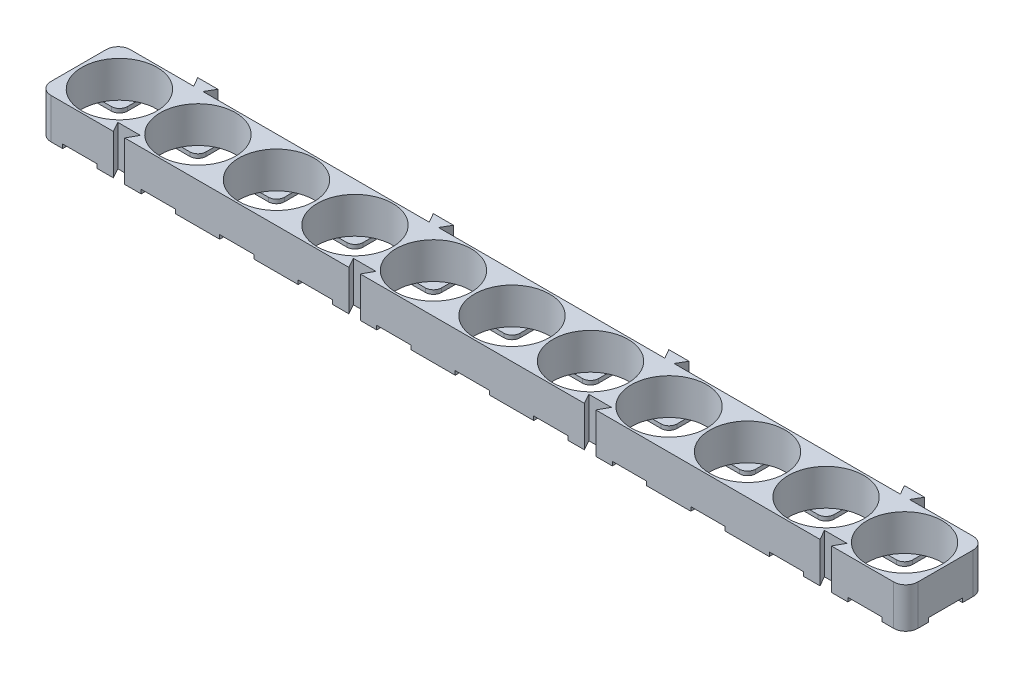
SolidWorks part; units mm, degrees
ref_plane "Front Plane" through (0, 0, 0) normal (0, 0, 1) x (1, 0, 0)
ref_plane "Top Plane" through (0, 0, 0) normal (0, 1, 0) x (1, 0, 0)
ref_plane "Right Plane" through (0, 0, 0) normal (1, 0, 0) x (0, 0, -1)
sketch "Sketch3" plane through (0, 0, 0) normal (0, 1, 0) x (1, 0, 0)
  line L0 (-10.15, 0) -> (9.35, 0) construction
  line L5 (9.35, 9.35) -> (9.35, -9.35) construction
  line L6 (9.35, -9.35) -> (-9.35, -9.35) construction
  line L7 (-9.35, -9.35) -> (-9.35, 9.35) construction
  line L8 (-9.35, 9.35) -> (9.35, 9.35) construction
  line L9 (10.15, -9.35) -> (10.15, 9.35) construction
  line L10 (10.15, 9.35) -> (28.85, 9.35) construction
  line L11 (28.85, 9.35) -> (28.85, -9.35) construction
  line L12 (28.85, -9.35) -> (10.15, -9.35) construction
  line L13 (29.65, -9.35) -> (29.65, 9.35) construction
  line L14 (29.65, 9.35) -> (48.35, 9.35) construction
  line L15 (48.35, 9.35) -> (48.35, -9.35) construction
  line L16 (48.35, -9.35) -> (29.65, -9.35) construction
  line L17 (49.15, -9.35) -> (49.15, 9.35) construction
  line L18 (49.15, 9.35) -> (67.85, 9.35) construction
  line L19 (67.85, 9.35) -> (67.85, -9.35) construction
  line L20 (67.85, -9.35) -> (49.15, -9.35) construction
  line L21 (68.65, -9.35) -> (68.65, 9.35) construction
  line L22 (68.65, 9.35) -> (87.35, 9.35) construction
  line L23 (87.35, 9.35) -> (87.35, -9.35) construction
  line L24 (87.35, -9.35) -> (68.65, -9.35) construction
  line L25 (88.15, -9.35) -> (88.15, 9.35) construction
  line L26 (88.15, 9.35) -> (106.85, 9.35) construction
  line L27 (106.85, 9.35) -> (106.85, -9.35) construction
  line L28 (106.85, -9.35) -> (88.15, -9.35) construction
  line L29 (107.65, -9.35) -> (107.65, 9.35) construction
  line L30 (107.65, 9.35) -> (126.35, 9.35) construction
  line L31 (126.35, 9.35) -> (126.35, -9.35) construction
  line L32 (126.35, -9.35) -> (107.65, -9.35) construction
  line L33 (127.15, -9.35) -> (127.15, 9.35) construction
  line L34 (127.15, 9.35) -> (145.85, 9.35) construction
  line L35 (145.85, 9.35) -> (145.85, -9.35) construction
  line L36 (145.85, -9.35) -> (127.15, -9.35) construction
  line L37 (146.65, -9.35) -> (146.65, 9.35) construction
  line L38 (146.65, 9.35) -> (165.35, 9.35) construction
  line L39 (165.35, 9.35) -> (165.35, -9.35) construction
  line L40 (165.35, -9.35) -> (146.65, -9.35) construction
  line L41 (166.15, -9.35) -> (166.15, 9.35) construction
  line L42 (166.15, 9.35) -> (184.85, 9.35) construction
  line L43 (184.85, 9.35) -> (184.85, -9.35) construction
  line L44 (184.85, -9.35) -> (166.15, -9.35) construction
  line L45 (185.65, -9.35) -> (185.65, 9.35) construction
  line L46 (185.65, 9.35) -> (204.35, 9.35) construction
  line L47 (204.35, 9.35) -> (204.35, -9.35) construction
  line L48 (204.35, -9.35) -> (185.65, -9.35) construction
  line L49 (-10.15, 0) -> (205.15, 0) construction
  line L50 (-10.15, 9.85) -> (205.15, 9.85)
  line L51 (-10.15, 9.85) -> (-10.15, -9.85)
  line L52 (-10.15, -9.85) -> (205.15, -9.85)
  line L53 (205.15, 9.85) -> (205.15, -9.85)
  line L54 (9.35, 9.35) -> (10.15, 9.35) construction
  line L55 (9.75, 28.55) -> (9.75, -9.85) construction
  line L56 (67.85, 9.35) -> (68.65, 9.35) construction
  line L57 (68.25, 9.35) -> (68.25, 13.7208) construction
  line L58 (12.25, 12.2) -> (7.25, 12.2)
  line L59 (7.25, 12.2) -> (8.6068, 9.85)
  line L60 (8.6068, 9.85) -> (10.8932, 9.85)
  line L61 (12.25, 12.2) -> (10.8932, 9.85)
  line L62 (12.55, -7.35) -> (6.95, -7.35)
  line L63 (6.95, -7.35) -> (8.3358, -9.85)
  line L64 (8.3358, -9.85) -> (11.1642, -9.85)
  line L65 (12.55, -7.35) -> (11.1642, -9.85)
  line L66 (67.1068, 9.85) -> (69.3932, 9.85)
  line L67 (70.75, 12.2) -> (69.3932, 9.85)
  line L68 (70.75, 12.2) -> (65.75, 12.2)
  line L69 (65.75, 12.2) -> (67.1068, 9.85)
  line L70 (66.8358, -9.85) -> (69.6642, -9.85)
  line L71 (71.05, -7.35) -> (69.6642, -9.85)
  line L72 (71.05, -7.35) -> (65.45, -7.35)
  line L73 (65.45, -7.35) -> (66.8358, -9.85)
  line L74 (125.6068, 9.85) -> (127.8932, 9.85)
  line L75 (129.25, 12.2) -> (127.8932, 9.85)
  line L76 (129.25, 12.2) -> (124.25, 12.2)
  line L77 (124.25, 12.2) -> (125.6068, 9.85)
  line L78 (125.3358, -9.85) -> (128.1642, -9.85)
  line L79 (129.55, -7.35) -> (128.1642, -9.85)
  line L80 (129.55, -7.35) -> (123.95, -7.35)
  line L81 (123.95, -7.35) -> (125.3358, -9.85)
  line L82 (184.1068, 9.85) -> (186.3932, 9.85)
  line L83 (187.75, 12.2) -> (186.3932, 9.85)
  line L84 (187.75, 12.2) -> (182.75, 12.2)
  line L85 (182.75, 12.2) -> (184.1068, 9.85)
  line L86 (183.8358, -9.85) -> (186.6642, -9.85)
  line L87 (188.05, -7.35) -> (186.6642, -9.85)
  line L88 (188.05, -7.35) -> (182.45, -7.35)
  line L89 (182.45, -7.35) -> (183.8358, -9.85)
  line L90 (68.25, 12.2) -> (68.25, 9.85) construction
  circle A0 centre (0, 0) radius 9.35
  circle A1 centre (19.5, 0) radius 9.35
  circle A2 centre (39, 0) radius 9.35
  circle A3 centre (58.5, 0) radius 9.35
  circle A4 centre (78, 0) radius 9.35
  circle A5 centre (97.5, 0) radius 9.35
  circle A6 centre (117, 0) radius 9.35
  circle A7 centre (136.5, 0) radius 9.35
  circle A8 centre (156, 0) radius 9.35
  circle A9 centre (175.5, 0) radius 9.35
  circle A10 centre (195, 0) radius 9.35
  point P10 (-0.4, 0)
  point P13 (-9.35, 0)
  point P16 (0, 9.35)
  point P84 (9.75, 9.35)
  point P88 (9.75, 9.85)
  point P89 (9.75, 12.2)
  point P94 (9.75, -7.35)
  dimension "D1" = 18.7
  dimension "D2" = 11
  dimension "D3" = 0.8
  dimension "D4" = 0.5
  dimension "D5" = 0.8
  dimension "D6" = 0.8
  dimension "D7" = 215.3
  dimension "D8" = 19.7
  dimension "D9" = 5
  dimension "D10" = 60
  dimension "D11" = 2.35
  dimension "D12" = 5.6
  dimension "D13" = 61
  dimension "D14" = 2.5
  dimension "D16" = 19.7
  dimension "D15" = 4
extrude "Boss-Extrude3" add sketch "Sketch3" along normal blind 10 contours L89 L88 L87 L52 L53 L50 L51 L63 L62 L65 L73 L72 L71 L81 L80 L79 A10 A9 A8 A7 A6 A5 A4 A3 A2 A1 A0 | L61 L58 L59 L50 | L68 L69 L50 L67 | L76 L77 L50 L75 | L84 L85 L50 L83 region at (-0.7716, 0, -9.6338) region at (9.75, 0, -11.1709) region at (68.25, 0, -11.1709) region at (126.75, 0, -11.1709) region at (185.25, 0, -11.1709)
extrude "Boss-Extrude6" add sketch "Sketch3<4>" along normal blind 1 contours A0 | A1 | A2 | A3 | A4 | A5 | A6 | A7 | A8 | A9 | A10 region at (0, 0, 0) region at (19.5, 0, 0) region at (39, 0, 0) region at (58.5, 0, 0) region at (78, 0, 0) region at (97.5, 0, 0) region at (117, 0, 0) region at (136.5, 0, 0) region at (156, 0, 0) region at (175.5, 0, 0) region at (195, 0, 0)
sketch "Sketch3<4>" plane through (0, 0, 0) normal (0, 1, 0) x (1, 0, 0) same geometry as "Sketch3"
sketch "Sketch8" plane through (0, 1, 0) normal (0, 1, 0) x (1, 0, 0)
  line L0 (-9.35, 0) -> (9.35, 0) construction
  line L1 (0, -9.35) -> (0, 9.35) construction
  line L2 (19.5, -9.35) -> (19.5, 9.35) construction
  line L3 (205.15, 9.85) -> (205.15, -9.85) construction
  line L4 (-10.15, -4.25) -> (205.15, -4.25)
  line L5 (-10.15, -4.25) -> (-10.15, 4.25)
  line L6 (-10.15, 4.25) -> (205.15, 4.25)
  line L7 (205.15, -4.25) -> (205.15, 4.25)
  line L8 (-10.15, -4.25) -> (205.15, 4.25) construction
  line L9 (-10.15, 4.25) -> (205.15, -4.25) construction
  line L10 (-10.15, 9.85) -> (8.6068, 9.85) construction
  line L11 (-4.25, -9.85) -> (4.25, -9.85)
  line L12 (-4.25, -9.85) -> (-4.25, 9.85)
  line L13 (-4.25, 9.85) -> (4.25, 9.85)
  line L14 (4.25, -9.85) -> (4.25, 9.85)
  line L15 (-4.25, -9.85) -> (4.25, 9.85) construction
  line L16 (-4.25, 9.85) -> (4.25, -9.85) construction
  line L17 (15.25, -9.85) -> (15.25, 9.85)
  line L18 (15.25, -9.85) -> (23.75, -9.85)
  line L19 (23.75, -9.85) -> (23.75, 9.85)
  line L20 (15.25, 9.85) -> (23.75, 9.85)
  line L21 (34.75, -9.85) -> (34.75, 9.85)
  line L22 (34.75, -9.85) -> (43.25, -9.85)
  line L23 (43.25, -9.85) -> (43.25, 9.85)
  line L24 (34.75, 9.85) -> (43.25, 9.85)
  line L25 (54.25, -9.85) -> (54.25, 9.85)
  line L26 (54.25, -9.85) -> (62.75, -9.85)
  line L27 (62.75, -9.85) -> (62.75, 9.85)
  line L28 (54.25, 9.85) -> (62.75, 9.85)
  line L29 (73.75, -9.85) -> (73.75, 9.85)
  line L30 (73.75, -9.85) -> (82.25, -9.85)
  line L31 (82.25, -9.85) -> (82.25, 9.85)
  line L32 (73.75, 9.85) -> (82.25, 9.85)
  line L33 (93.25, -9.85) -> (93.25, 9.85)
  line L34 (93.25, -9.85) -> (101.75, -9.85)
  line L35 (101.75, -9.85) -> (101.75, 9.85)
  line L36 (93.25, 9.85) -> (101.75, 9.85)
  line L37 (112.75, -9.85) -> (112.75, 9.85)
  line L38 (112.75, -9.85) -> (121.25, -9.85)
  line L39 (121.25, -9.85) -> (121.25, 9.85)
  line L40 (112.75, 9.85) -> (121.25, 9.85)
  line L41 (132.25, -9.85) -> (132.25, 9.85)
  line L42 (132.25, -9.85) -> (140.75, -9.85)
  line L43 (140.75, -9.85) -> (140.75, 9.85)
  line L44 (132.25, 9.85) -> (140.75, 9.85)
  line L45 (151.75, -9.85) -> (151.75, 9.85)
  line L46 (151.75, -9.85) -> (160.25, -9.85)
  line L47 (160.25, -9.85) -> (160.25, 9.85)
  line L48 (151.75, 9.85) -> (160.25, 9.85)
  line L49 (171.25, -9.85) -> (171.25, 9.85)
  line L50 (171.25, -9.85) -> (179.75, -9.85)
  line L51 (179.75, -9.85) -> (179.75, 9.85)
  line L52 (171.25, 9.85) -> (179.75, 9.85)
  line L53 (190.75, -9.85) -> (190.75, 9.85)
  line L54 (190.75, -9.85) -> (199.25, -9.85)
  line L55 (199.25, -9.85) -> (199.25, 9.85)
  line L56 (190.75, 9.85) -> (199.25, 9.85)
  line L57 (15.25, 9.85) -> (23.75, -9.85) construction
  circle A2 centre (0, 0) radius 9.35
  circle A3 centre (0, 0) radius 9.35 construction
  circle A5 centre (19.5, 0) radius 9.35
  circle A6 centre (19.5, 0) radius 9.35 construction
  point P3 (0, 0)
  point P12 (0, 0)
  point P14 (19.5, 0)
  point P15 (97.5, 0)
  dimension "D3" = 19.5
  dimension "D4" = 8.5
  dimension "D5" = 11
  dimension "D1" = 0
  dimension "D2" = 0
extrude "Cut-Extrude4" cut sketch "Sketch8" against normal through all contours L6 L7 L4 L5 | L12 L13 L14 L11 | L17 L20 L19 L18 | L21 L24 L23 L22 | L25 L28 L27 L26 | L29 L32 L31 L30 | L33 L36 L35 L34 | L37 L40 L39 L38 | L41 L44 L43 L42 | L45 L48 L47 L46 | L49 L52 L51 L50 | L53 L56 L55 L54
fillet "Fillet3" radius 2 44 edges at (4.25, 0.5, -4.25) (-4.25, 0.5, -4.25) (4.25, 0.5, 4.25) (-4.25, 0.5, 4.25) (190.75, 0.5, -4.25) (190.75, 0.5, 4.25) (171.25, 0.5, -4.25) (171.25, 0.5, 4.25) (151.75, 0.5, 4.25) (151.75, 0.5, -4.25) (132.25, 0.5, -4.25) (132.25, 0.5, 4.25) (112.75, 0.5, -4.25) (93.25, 0.5, 4.25) (93.25, 0.5, -4.25) (73.75, 0.5, 4.25) (73.75, 0.5, -4.25) (54.25, 0.5, -4.25) (54.25, 0.5, 4.25) (34.75, 0.5, 4.25) (62.75, 0.5, -4.25) (62.75, 0.5, 4.25) (82.25, 0.5, -4.25) (82.25, 0.5, 4.25) (101.75, 0.5, -4.25) (101.75, 0.5, 4.25) (121.25, 0.5, -4.25) (121.25, 0.5, 4.25) (140.75, 0.5, 4.25) (140.75, 0.5, -4.25) (160.25, 0.5, -4.25) (160.25, 0.5, 4.25) (179.75, 0.5, 4.25) (179.75, 0.5, -4.25) (199.25, 0.5, -4.25) (199.25, 0.5, 4.25) (43.25, 0.5, 4.25) (43.25, 0.5, -4.25) (23.75, 0.5, -4.25) (23.75, 0.5, 4.25) (15.25, 0.5, 4.25) (15.25, 0.5, -4.25) (34.75, 0.5, -4.25) (112.75, 0.5, 4.25)
fillet "Fillet4" radius 3 4 edges at (205.15, 5, 9.85) (205.15, 5, -9.85) (-10.15, 5, 9.85) (-10.15, 5, -9.85)
equation "\"`\"=10"
